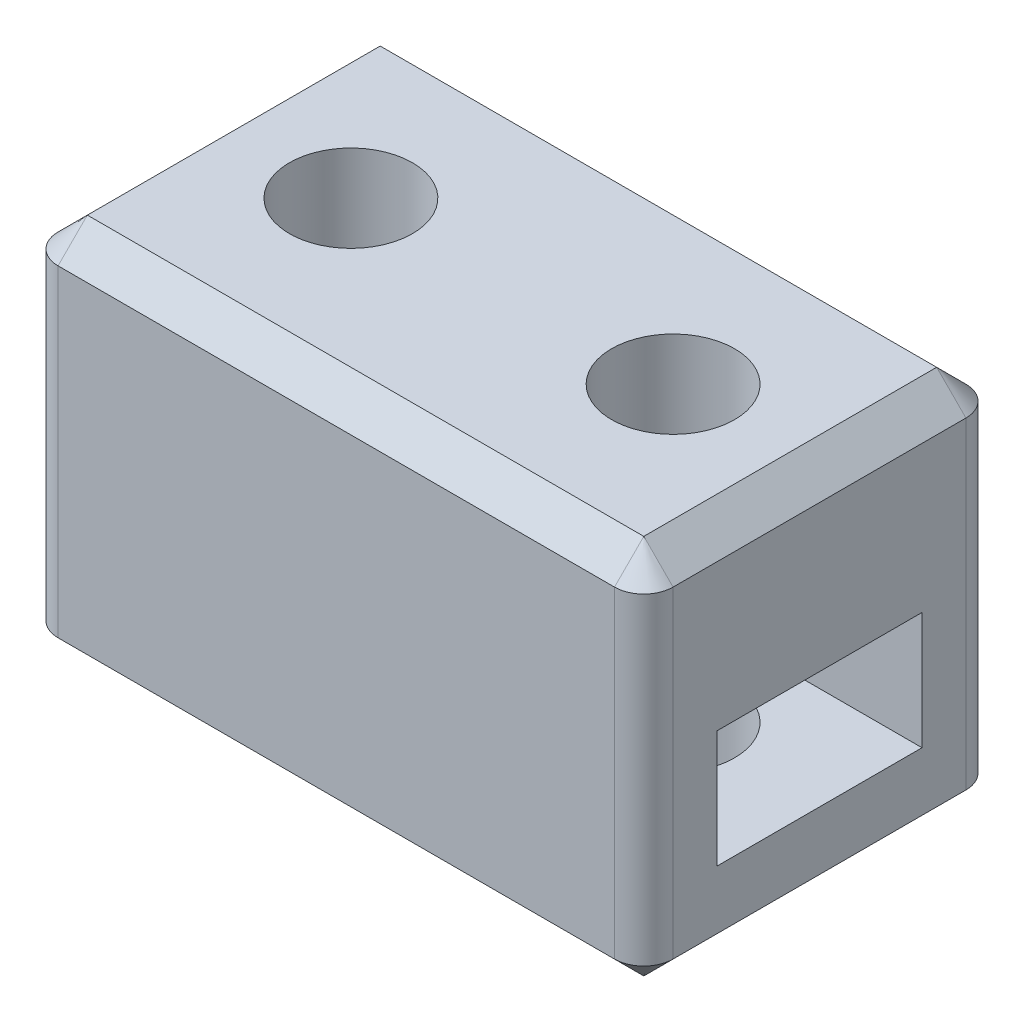
SolidWorks part; units mm, degrees
ref_plane "Front Plane" through (0, 0, 0) normal (0, 0, 1) x (1, 0, 0)
ref_plane "Top Plane" through (0, 0, 0) normal (0, 1, 0) x (1, 0, 0)
ref_plane "Right Plane" through (0, 0, 0) normal (1, 0, 0) x (0, 0, -1)
sketch "Sketch2" plane through (0, 0, 0) normal (0, 1, 0) x (1, 0, 0)
  line L0 (-5.5, 0) -> (5.5, 0) construction
  line L1 (-10.5, 6) -> (10.5, 6)
  line L2 (-10.5, 6) -> (-10.5, -6)
  line L3 (-10.5, -6) -> (10.5, -6)
  line L4 (10.5, 6) -> (10.5, -6)
  line L5 (-10.5, 6) -> (10.5, -6) construction
  line L6 (-10.5, -6) -> (10.5, 6) construction
  circle A0 centre (-5.5, 0) radius 2.1
  circle A1 centre (5.5, 0) radius 2.1
  point P0 (0, 0)
  dimension "D2" = 4.2
  dimension "D3" = 4.2
  dimension "D1" = 12
  dimension "D4" = 5
  dimension "D5" = 11
extrude "Boss-Extrude1" add sketch "Sketch2" along normal blind 13
sketch "Sketch7" plane through (10.5, 0, 0) normal (1, 0, 0) x (0, 0, -1)
  line L0 (0, 0) -> (0, 13) construction
  line L1 (-6, 13) -> (6, 13) construction
  line L2 (-6, 0) -> (6, 0) construction
  line L3 (-3.5, 7) -> (3.5, 7)
  line L4 (-3.5, 7) -> (-3.5, 3)
  line L5 (-3.5, 3) -> (3.5, 3)
  line L6 (3.5, 7) -> (3.5, 3)
  line L7 (-3.5, 7) -> (3.5, 3) construction
  line L8 (-3.5, 3) -> (3.5, 7) construction
  point P5 (0, 5)
  dimension "D1" = 4
  dimension "D2" = 7
  dimension "D3" = 3
extrude "Cut-Extrude3" cut sketch "Sketch7" against normal blind 10
mirror "Mirror1" about plane through (0, 0, 0) normal (1, 0, 0) of "Cut-Extrude3"
fillet "Fillet1" radius 1 4 edges at (-10.5, 6.5, 6) (-10.5, 6.5, -6) (10.5, 6.5, -6) (10.5, 6.5, 6)
chamfer "Chamfer1" distance 1 angle 45 16 edges at (0, 0, -6) (-10.2071, 0, -5.7071) (10.2071, 0, -5.7071) (-10.5, 0, 0) (10.5, 0, 0) (-10.2071, 0, 5.7071) (10.2071, 0, 5.7071) (0, 0, 6) (0, 13, -6) (-10.2071, 13, -5.7071) (10.2071, 13, -5.7071) (-10.5, 13, 0) (10.5, 13, 0) (-10.2071, 13, 5.7071) (10.2071, 13, 5.7071) (0, 13, 6)
